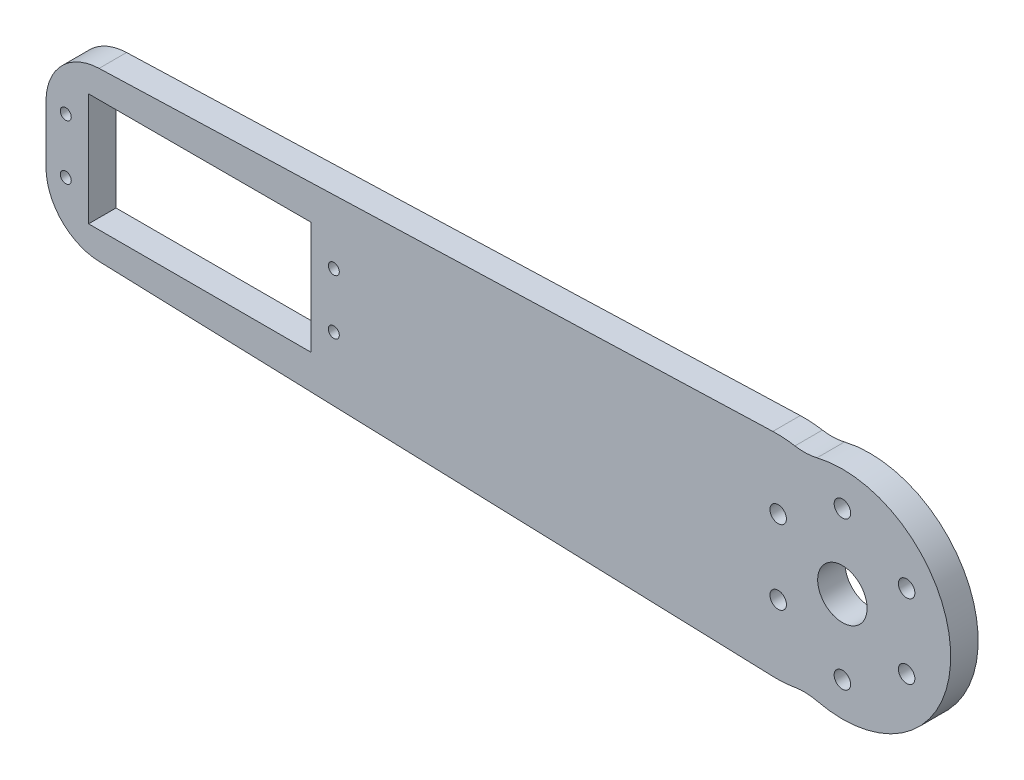
SolidWorks part; units mm, degrees
ref_plane "Front Plane" through (0, 0, 0) normal (0, 0, 1) x (1, 0, 0)
ref_plane "Top Plane" through (0, 0, 0) normal (0, 1, 0) x (1, 0, 0)
ref_plane "Right Plane" through (0, 0, 0) normal (1, 0, 0) x (0, 0, -1)
sketch "Sketch1" plane through (0, 0, 0) normal (0, 0, 1) x (1, 0, 0)
  line L0 (-75, 0) -> (-70, 0) construction
  line L5 (-75, 15) -> (75, -15) construction
  line L6 (-75, -15) -> (75, 15) construction
  line L7 (-70, 0) -> (-30, 0) construction
  line L8 (75, 0) -> (70, 0) construction
  line L9 (-70.25, 10.25) -> (-29.75, 10.25)
  line L10 (-70.25, 10.25) -> (-70.25, -10.25)
  line L11 (-70.25, -10.25) -> (-29.75, -10.25)
  line L12 (-29.75, 10.25) -> (-29.75, -10.25)
  line L13 (-70.25, 10.25) -> (-29.75, -10.25) construction
  line L14 (-70.25, -10.25) -> (-29.75, 10.25) construction
  line L15 (70, 0) -> (64, 0) construction
  line L16 (75, 20) -> (75, -20)
  line L17 (75, 20) -> (-75, 15)
  line L18 (75, -20) -> (-75, -15)
  line L19 (-75, 15) -> (-78, 15)
  line L20 (-78, 15) -> (-78, -15)
  line L21 (-78, -15) -> (-75, -15)
  circle A0 centre (67, 0) radius 3
  point P0 (0, 0)
  point P9 (-50, 0)
  point P22 (75, 0)
extrude "Boss-Extrude1" add sketch "Sketch1" along normal blind 5
fillet "Fillet2" radius 20 2 edges at (75, -20, 2.5) (75, 20, 2.5)
sketch "Sketch3" plane through (0, 0, 5) normal (0, 0, 1) x (1, 0, 0)
  circle A0 centre (67, 0) radius 19.7224
  circle A1 centre (67, 0) radius 3
extrude "Boss-Extrude2" add sketch "Sketch3" against normal up to surface (5 mm away) up to face at (-16.3355, 0, 0)
fillet "Fillet3" radius 10 4 edges at (-78, 15, 2.5) (-78, -15, 2.5) (60.3908, -18.582, 2.5) (60.3908, 18.582, 2.5)
sketch "Sketch4" plane through (0, 0, 0) normal (0, 0, -1) x (-1, 0, 0)
  line L0 (50, 10.25) -> (50, -10.25) construction
  line L1 (29.75, -10.25) -> (29.75, 10.25) construction
  line L2 (29.75, -10.25) -> (29.75, -5) construction
  line L3 (29.75, -5) -> (25.6, -5) construction
  line L4 (29.75, 10.25) -> (70.25, 10.25) construction
  line L5 (70.25, -10.25) -> (29.75, -10.25) construction
  line L6 (29.75, 0) -> (70.25, 0) construction
  line L7 (70.25, 10.25) -> (70.25, -10.25) construction
  circle A0 centre (25.6, -5) radius 1
  circle A1 centre (25.6, 5) radius 1
  circle A2 centre (74.4, 5) radius 1
  circle A3 centre (74.4, -5) radius 1
extrude "Cut-Extrude1" cut sketch "Sketch4" against normal blind 6
sketch "Sketch5" plane through (0, 0, 5) normal (0, 0, 1) x (1, 0, 0)
  circle A1 centre (67, 13.5) radius 1.5
extrude "Cut-Extrude2" cut sketch "Sketch5" against normal blind 6
sketch "Sketch6" plane through (0, 0, 5) normal (0, 0, 1) x (1, 0, 0)
  circle A0 centre (67, 0) radius 4.5
extrude "Cut-Extrude3" cut sketch "Sketch6" against normal blind 6
pattern_circular "CirPattern1" count 6 every 60 about axis through (67, 0, -1) along (0, 0, 1) of "Cut-Extrude2"
